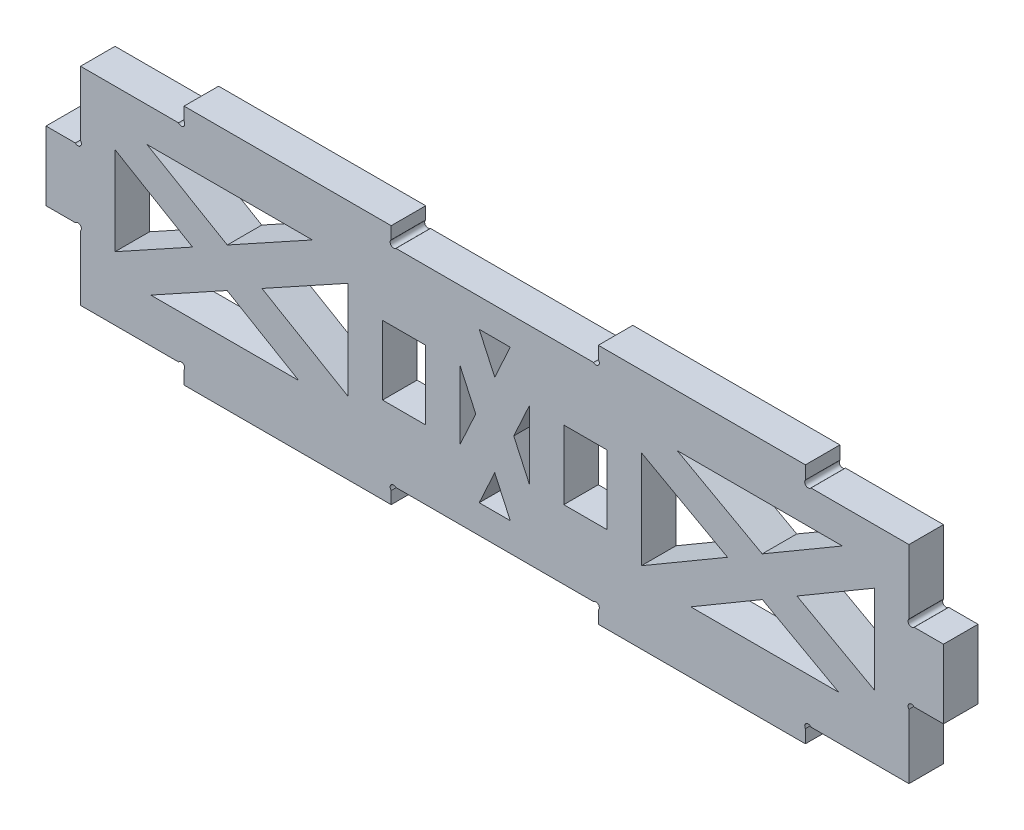
SolidWorks part; units mm, degrees
material "7050-T73510"
ref_plane "Front Plane" through (0, 0, 0) normal (0, 0, 1) x (1, 0, 0)
ref_plane "Top Plane" through (0, 0, 0) normal (0, 1, 0) x (1, 0, 0)
ref_plane "Right Plane" through (0, 0, 0) normal (1, 0, 0) x (0, 0, -1)
sketch "Sketch1" plane through (0, 0, 0) normal (0, 0, 1) x (1, 0, 0)
  line L1 (-165.1, -38.1) -> (165.1, -38.1)
  line L2 (-165.1, -38.1) -> (-165.1, 38.1)
  line L3 (-165.1, 38.1) -> (165.1, 38.1)
  line L4 (165.1, -38.1) -> (165.1, 38.1)
  line L5 (-165.1, -38.1) -> (165.1, 38.1) construction
  line L6 (-165.1, 38.1) -> (165.1, -38.1) construction
  point P0 (0, 0)
  dimension "D1" = 330.2
  dimension "D2" = 76.2
extrude "Boss-Extrude1" add sketch "Sketch1" along normal blind 12.7 contours L1 L3 region at (0, 0, 0)
sketch "Sketch2" plane through (0, 0, 12.7) normal (0, 0, 1) x (1, 0, 0)
  line L0 (-165.1, -38.1) -> (165.1, -38.1) construction
  line L1 (-38.1, -38.1) -> (-114.3, -38.1)
  line L2 (-38.1, -38.1) -> (-38.1, -44.45)
  line L3 (-38.1, -44.45) -> (-114.3, -44.45)
  line L4 (-114.3, -38.1) -> (-114.3, -44.45)
  line L5 (0, -6.985) -> (0, 6.985) construction
  line L6 (38.1, -44.45) -> (114.3, -44.45)
  line L7 (114.3, -38.1) -> (114.3, -44.45)
  line L8 (38.1, -38.1) -> (114.3, -38.1)
  line L9 (38.1, -38.1) -> (38.1, -44.45)
  line L10 (6.985, 0) -> (-6.985, 0) construction
  line L11 (38.1, 38.1) -> (38.1, 44.45)
  line L12 (38.1, 38.1) -> (114.3, 38.1)
  line L13 (114.3, 38.1) -> (114.3, 44.45)
  line L14 (38.1, 44.45) -> (114.3, 44.45)
  line L15 (-38.1, 44.45) -> (-114.3, 44.45)
  line L16 (-114.3, 38.1) -> (-114.3, 44.45)
  line L17 (-38.1, 38.1) -> (-114.3, 38.1)
  line L18 (-38.1, 38.1) -> (-38.1, 44.45)
  point P12 (-38.1, -41.275)
  dimension "D1" = 76.2
  dimension "D2" = 6.35
  dimension "D3" = 76.2
extrude "Boss-Extrude2" add sketch "Sketch2" against normal blind 12.7
sketch "Sketch3" plane through (0, 0, 12.7) normal (0, 0, 1) x (1, 0, 0)
  line L0 (6.985, 0) -> (-6.985, 0) construction
  line L1 (-165.1, -38.1) -> (-152.4, -38.1)
  line L2 (-165.1, -38.1) -> (-165.1, -12.7)
  line L3 (-165.1, -12.7) -> (-152.4, -12.7)
  line L4 (-152.4, -38.1) -> (-152.4, -12.7)
  line L6 (-165.1, 12.7) -> (-152.4, 12.7)
  line L7 (-152.4, 38.1) -> (-152.4, 12.7)
  line L8 (-165.1, 38.1) -> (-152.4, 38.1)
  line L9 (-165.1, 38.1) -> (-165.1, 12.7)
  line L10 (0, -6.985) -> (0, 6.985) construction
  line L11 (165.1, 38.1) -> (165.1, 12.7)
  line L12 (165.1, 38.1) -> (152.4, 38.1)
  line L13 (152.4, 38.1) -> (152.4, 12.7)
  line L14 (165.1, 12.7) -> (152.4, 12.7)
  line L15 (165.1, -12.7) -> (152.4, -12.7)
  line L16 (152.4, -38.1) -> (152.4, -12.7)
  line L17 (165.1, -38.1) -> (152.4, -38.1)
  line L18 (165.1, -38.1) -> (165.1, -12.7)
  line L19 (25.4, 12.7) -> (41.275, 12.7)
  line L20 (25.4, 12.7) -> (25.4, -12.7)
  line L21 (25.4, -12.7) -> (41.275, -12.7)
  line L22 (41.275, 12.7) -> (41.275, -12.7)
  line L23 (-38.1, -38.1) -> (38.1, -38.1) construction
  line L24 (-25.4, -12.7) -> (-41.275, -12.7)
  line L25 (-41.275, 12.7) -> (-41.275, -12.7)
  line L26 (-25.4, 12.7) -> (-41.275, 12.7)
  line L27 (-25.4, 12.7) -> (-25.4, -12.7)
  line L28 (-38.1, 38.1) -> (38.1, 38.1) construction
  dimension "D1" = 25.4
  dimension "D2" = 12.7
  dimension "D3" = 50.8
  dimension "D4" = 15.875
  dimension "D5" = 25.4
  dimension "D6" = 25.4
extrude "Cut-Extrude1" cut sketch "Sketch3" against normal through all
sketch "Sketch4" plane through (0, 0, 12.7) normal (0, 0, 1) x (1, 0, 0)
  line L0 (6.985, 0) -> (-6.985, 0) construction
  line L1 (-139.7, -21.8966) -> (-53.975, -21.8966)
  line L2 (-139.7, -21.8966) -> (-139.7, 25.4)
  line L3 (-139.7, 25.4) -> (-53.975, 25.4)
  line L4 (-53.975, -21.8966) -> (-53.975, 25.4)
  line L5 (-139.7, -21.8966) -> (-104.8218, -2.6534) construction
  line L6 (0, -6.985) -> (0, 6.985) construction
  line L7 (-152.4, 12.7) -> (-152.4, 38.1) construction
  line L8 (-41.275, 12.7) -> (-41.275, -12.7) construction
  line L9 (-152.4, 38.1) -> (-114.3, 38.1) construction
  line L10 (-139.7, 17.8609) -> (-111.1841, 1.0887)
  line L11 (-126.5551, -21.8966) -> (-98.4595, -6.3955)
  line L12 (-127.9201, 25.4) -> (-98.411, 8.136)
  line L13 (-139.7, -14.6442) -> (-111.1841, 1.0887)
  line L14 (-136.6325, -27.4565) -> (-50.9075, 19.8401) construction
  line L15 (-142.7675, -16.3366) -> (-57.0425, 30.9599) construction
  line L16 (100.0125, 0) -> (93.9285, 3.3567) construction
  line L17 (139.7, -21.8966) -> (104.8218, -2.6534) construction
  line L18 (-98.411, 8.136) -> (-67.1199, 25.4)
  line L19 (85.6513, 0.6711) -> (53.975, -17.8609)
  line L20 (-100.0125, 0) -> (-93.9285, 3.3567) construction
  line L21 (-139.7, -21.8966) -> (-53.975, 25.4) construction
  line L22 (-85.6513, 0.6711) -> (-53.975, 18.1476)
  line L23 (-98.4595, -6.3955) -> (-72.1049, -21.8966)
  line L24 (-85.6513, 0.6711) -> (-53.975, -17.8609)
  line L25 (98.4595, -6.3955) -> (72.1049, -21.8966)
  line L26 (85.6513, 0.6711) -> (53.975, 18.1476)
  line L27 (98.411, 8.136) -> (67.1199, 25.4)
  line L28 (139.7, -14.6442) -> (111.1841, 1.0887)
  line L29 (127.9201, 25.4) -> (98.411, 8.136)
  line L30 (126.5551, -21.8966) -> (98.4595, -6.3955)
  line L31 (139.7, 17.8609) -> (111.1841, 1.0887)
  line L32 (53.975, -21.8966) -> (53.975, 25.4)
  line L33 (139.7, 25.4) -> (53.975, 25.4)
  line L34 (139.7, -21.8966) -> (139.7, 25.4)
  line L35 (139.7, -21.8966) -> (53.975, -21.8966)
  line L36 (-25.4, -12.7) -> (-25.4, 12.7) construction
  line L41 (-12.7, 12.4271) -> (5.7115, -27.6329)
  line L42 (-12.7, -27.6329) -> (12.7, -27.6329)
  line L44 (-12.7, -27.6329) -> (-12.7, 27.6329)
  line L45 (-12.7, 27.6329) -> (12.7, 27.6329)
  line L46 (12.7, -27.6329) -> (12.7, 27.6329)
  line L47 (-12.7, -27.6329) -> (12.7, 27.6329) construction
  line L48 (-12.7, 27.6329) -> (12.7, -27.6329) construction
  line L49 (-5.7115, -27.6329) -> (12.7, 12.4271)
  line L50 (-5.7115, 27.6329) -> (12.7, -12.4271)
  line L51 (-12.7, -12.4271) -> (5.7115, 27.6329)
  line L52 (-6.9302, -30.2847) -> (18.4698, 24.9812) construction
  line L53 (-18.4698, -24.9812) -> (6.9302, 30.2847) construction
  line L54 (-18.4698, 24.9812) -> (6.9302, -30.2847) construction
  line L55 (-6.9302, 30.2847) -> (18.4698, -24.9812) construction
  point P0 (-100.0125, 0)
  point P53 (100.0125, 0)
  point P54 (0, 0)
  dimension "D1" = 12.7
  dimension "D2" = 12.7
  dimension "D3" = 12.7
  dimension "D6" = 12.7
  dimension "D7" = 6.35
  dimension "D4" = 6.35
  dimension "D5" = 6.35
  dimension "D8" = 6.35
extrude "Cut-Extrude2" cut sketch "Sketch4" against normal through all contours L22 L24 L4 | L2 L13 L10 | L12 L18 L3 | L23 L11 L1 | L32 L19 L26 | L35 L30 L25 | L29 L33 L27 | L28 L34 L31 | L45 | L44 | L46 | L42 region at (-99.0398, -16.7295, 12.7) region at (-130.1947, 1.4351, 12.7) region at (-64.5338, 0.3193, 12.7) region at (-97.817, 19.6453, 12.7) region at (64.5338, 0.3193, 12.7) region at (99.0398, -16.7295, 12.7) region at (97.817, 19.6453, 12.7) region at (130.1947, 1.4351, 12.7) region at (-10.7962, 0, 12.7) region at (0, -23.4906, 12.7) region at (0, 23.4906, 12.7) region at (10.7962, 0, 12.7)
sketch "Sketch7" plane through (0, 0, 12.7) normal (0, 0, 1) x (1, 0, 0)
  line L0 (0, -6.985) -> (0, 6.985) construction
  line L1 (6.985, 0) -> (-6.985, 0) construction
  circle A0 centre (-153.3572, -13.5347) radius 1.27
  circle A1 centre (-115.3222, -38.8536) radius 1.27
  circle A2 centre (-37.2199, -39.0156) radius 1.27
  circle A3 centre (37.2199, -39.0156) radius 1.27
  circle A4 centre (115.3222, -38.8536) radius 1.27
  circle A5 centre (153.3572, -13.5347) radius 1.27
  circle A6 centre (153.3572, 13.5347) radius 1.27
  circle A7 centre (115.3222, 38.8536) radius 1.27
  circle A8 centre (37.2199, 39.0156) radius 1.27
  circle A9 centre (-37.2199, 39.0156) radius 1.27
  circle A10 centre (-115.3222, 38.8536) radius 1.27
  circle A11 centre (-153.3572, 13.5347) radius 1.27
extrude "Cut-Extrude4" cut sketch "Sketch7" against normal through all
